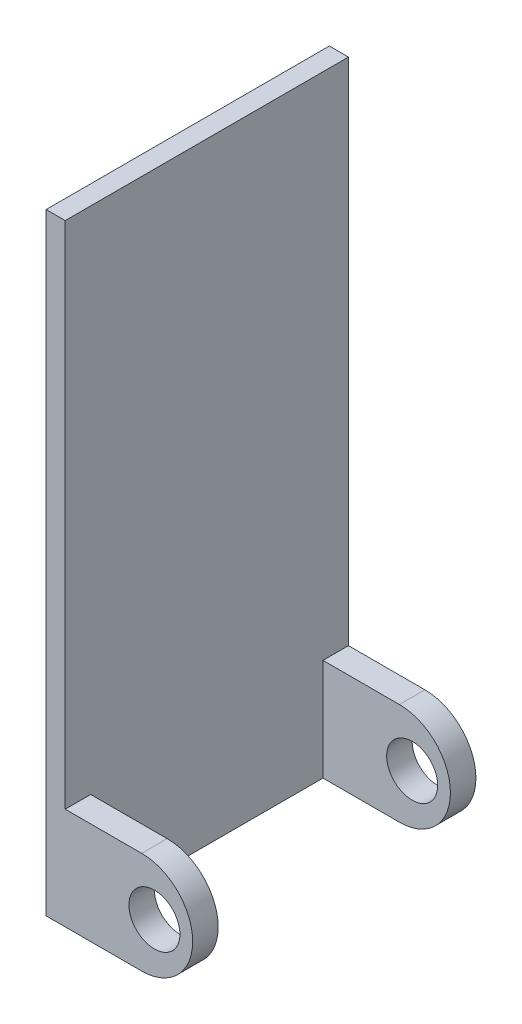
SolidWorks part; units mm, degrees
ref_plane "Front Plane" through (0, 0, 0) normal (0, 0, 1) x (1, 0, 0)
ref_plane "Top Plane" through (0, 0, 0) normal (0, 1, 0) x (1, 0, 0)
ref_plane "Right Plane" through (0, 0, 0) normal (1, 0, 0) x (0, 0, -1)
sketch "Sketch1" plane through (0, 0, 0) normal (0, 0, 1) x (1, 0, 0)
  line L1 (1.5, 48) -> (-1.5, 48)
  line L2 (1.5, 48) -> (1.5, -48)
  line L3 (1.5, -48) -> (-1.5, -48)
  line L4 (-1.5, 48) -> (-1.5, -48)
  line L5 (1.5, 48) -> (-1.5, -48) construction
  line L6 (1.5, -48) -> (-1.5, 48) construction
  point P0 (0, 0)
  dimension "D1" = 3
  dimension "D2" = 96
extrude "Boss-Extrude1" add sketch "Sketch1" along normal blind 44.45
sketch "Sketch2" plane through (0, 0, 44.45) normal (0, 0, 1) x (1, 0, 0)
  line L0 (-1.5, 48) -> (-1.5, -48) construction
  line L1 (-1.5, -48) -> (1.5, -48) construction
  line L2 (15.5, 40) -> (15.5, -40) construction
  line L4 (1.5, 48) -> (21.5, 48)
  line L5 (1.5, 48) -> (1.5, 32)
  line L6 (1.5, 32) -> (21.5, 32)
  line L7 (21.5, 48) -> (21.5, 32)
  line L8 (1.5, -48) -> (21.5, -48)
  line L9 (1.5, -48) -> (1.5, -32)
  line L10 (1.5, -32) -> (21.5, -32)
  line L11 (21.5, -48) -> (21.5, -32)
  line L12 (1.5, 48) -> (-1.5, 48) construction
  circle A0 centre (15.5, 40) radius 4
  circle A1 centre (15.5, -40) radius 4
  line M11 (1.5, -48) -> (1.5, 48)
  dimension "D3" = 8
  dimension "D1" = 8
  dimension "D2" = 17
  dimension "D4" = 8
  dimension "D5" = 16
  dimension "D6" = 20
extrude "Boss-Extrude2" add sketch "Sketch2" against normal blind 4 contours L8 L11 L10 A1 M11 region at (10.7546, -40, 44.45)
fillet "Fillet1" [suppressed] type full round
fillet "Fillet2" 2 edges at (21.5, -32, 42.45) (21.5, -48, 42.45) type full round first side face at (11.5, -32, 42.45) second side face at (7.1667, -48, 28.3) middle face at (21.5, -40, 42.45)
ref_plane "Plane1" through (0, 0, 22.225) normal (0, 0, 1) x (1, 0, 0)
ref_plane "Plane2" through (0, 0, 22.725) normal (0, 0, 1) x (1, 0, 0)
sketch "Sketch3" plane through (0, 0, 22.725) normal (0, 0, 1) x (1, 0, 0)
  line L0 (1.5, -48) -> (1.5, 48) construction
  line L1 (1.5, 39.508) -> (9.5, 39.508)
  line L2 (1.5, 39.508) -> (1.5, 47.508)
  line L3 (1.5, 47.508) -> (9.5, 47.508)
  line L4 (9.5, 39.508) -> (9.5, 47.508)
  circle A0 centre (7, 43.508) radius 1.5
  dimension "D3" = 3
  dimension "D1" = 8
  dimension "D2" = 8
  dimension "D4" = 2.5
  dimension "D5" = 4
  dimension "D6" = 0.492
extrude "Boss-Extrude4" [suppressed] add sketch "Sketch3" along normal blind 4
mirror "Mirror2" about plane through (0, 0, 22.225) normal (0, 0, 1) of "Fillet2", "Boss-Extrude2"
